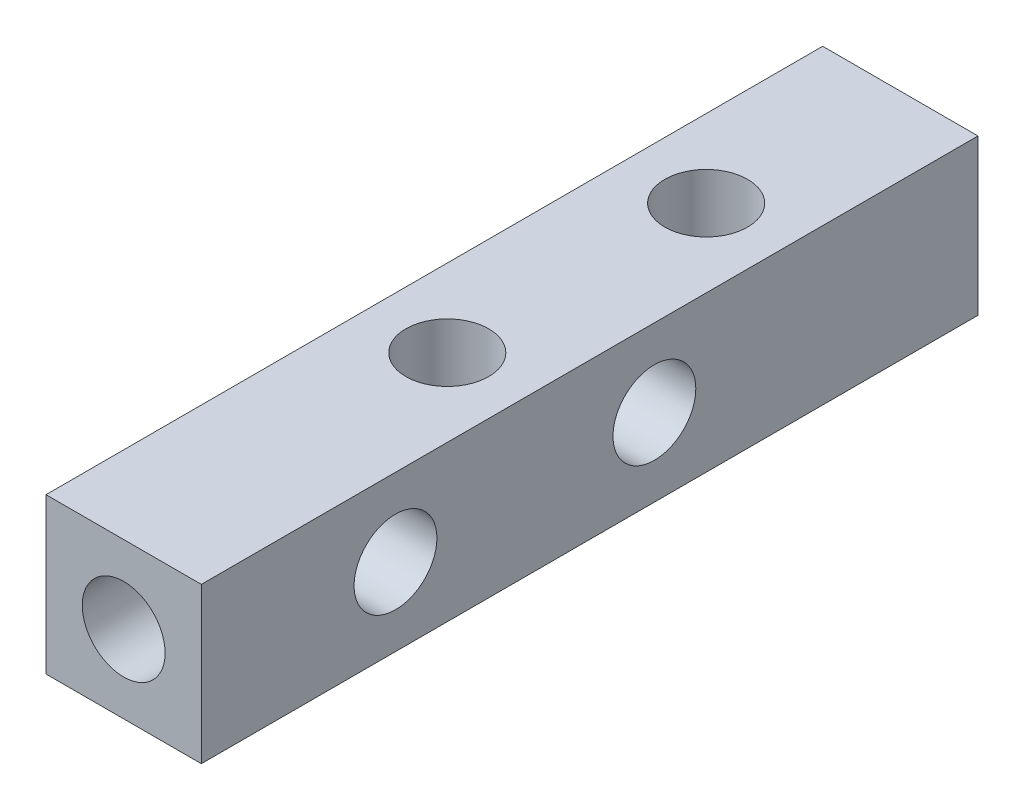
SolidWorks part; units mm, degrees
material "6061 合金"
ref_plane "前视基准面" through (0, 0, 0) normal (0, 0, 1) x (1, 0, 0)
ref_plane "上视基准面" through (0, 0, 0) normal (0, 1, 0) x (1, 0, 0)
ref_plane "右视基准面" through (0, 0, 0) normal (1, 0, 0) x (0, 0, -1)
sketch "草图1" plane through (0, 0, 0) normal (0, 0, 1) x (1, 0, 0)
  line L0 (0, 0) -> (6, 0)
  line L1 (6, 0) -> (6, 6)
  line L2 (6, 6) -> (0, 6)
  line L3 (0, 6) -> (0, 0)
extrude "凸台-拉伸1" add sketch "草图1" along normal blind 30
sketch "草图2" plane through (0, 0, 30) normal (0, 0, 1) x (1, 0, 0)
  circle A0 centre (3, 3) radius 1.6
extrude "切除-拉伸1" cut sketch "草图2" against normal blind 5
extrude "切除-拉伸2" cut sketch "草图2<2>" along normal blind 5 from surface starting at face at (3, 3, 0)
sketch "草图2<2>" plane through (0, 0, 30) normal (0, 0, 1) x (1, 0, 0) same geometry as "草图2"
sketch "草图3" plane through (6, 0, 0) normal (1, 0, 0) x (0, 0, -1)
  circle A0 centre (-22.5, 3) radius 1.6
  circle A1 centre (-12.5, 3) radius 1.6
extrude "切除-拉伸3" cut sketch "草图3" against normal blind 7
sketch "草图4" plane through (0, 6, 0) normal (0, 1, 0) x (1, 0, 0)
  circle A0 centre (3, -7.5) radius 1.6
  circle A1 centre (3, -17.5) radius 1.6
extrude "切除-拉伸4" cut sketch "草图4" against normal blind 7
